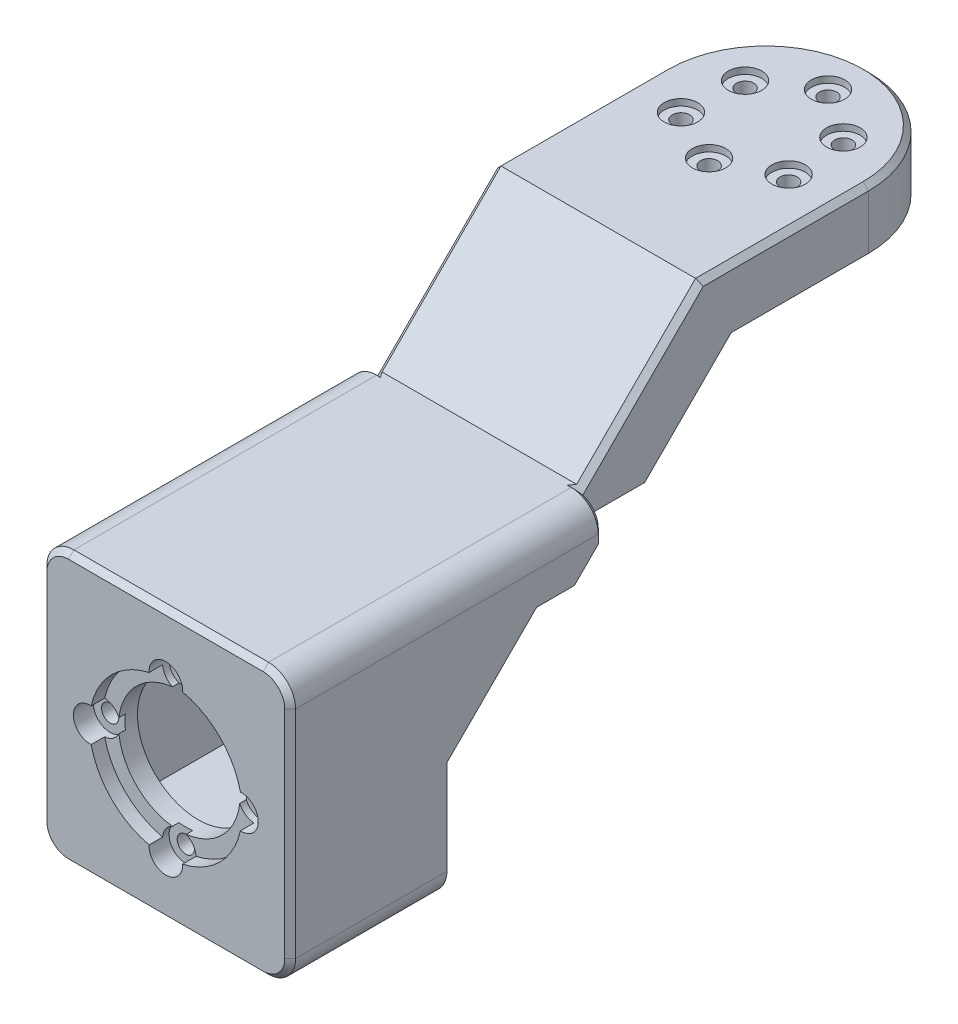
SolidWorks part; units mm, degrees
ref_plane "前视基准面" through (0, 0, 0) normal (0, 0, 1) x (1, 0, 0)
ref_plane "上视基准面" through (0, 0, 0) normal (0, 1, 0) x (1, 0, 0)
ref_plane "右视基准面" through (0, 0, 0) normal (1, 0, 0) x (0, 0, -1)
other "Configuration Table"
sketch "草图1" plane through (0, 0, 0) normal (0, 1, 0) x (1, 0, 0)
  circle A0 centre (0, 0) radius 19
  dimension "D1" = 38
extrude "凸台-拉伸1" add sketch "草图1" along normal blind 6
sketch "草图2" plane through (0, 6, 0) normal (0, 1, 0) x (1, 0, 0)
  line L0 (-19, 0) -> (19, 0) construction
  line L2 (-19, 0) -> (19, 0)
  line L3 (-19, 0) -> (-19, -25)
  line L4 (-19, -25) -> (19, -25)
  line L5 (19, 0) -> (19, -25)
  circle A0 centre (0, 0) radius 19 construction
  dimension "D1" = 25
extrude "凸台-拉伸2" add sketch "草图2" against normal up to surface (6 mm away) up to face at (0, 0, 19)
sketch "草图3" plane through (0, 6, 0) normal (0, 1, 0) x (1, 0, 0)
  line L1 (-19, -25) -> (19, -25)
  line L2 (-19, -25) -> (-19, -31)
  line L3 (-19, -31) -> (19, -31)
  line L4 (19, -25) -> (19, -31)
  dimension "D1" = 6
extrude "凸台-拉伸3" add sketch "草图3" against normal blind 28
sketch "草图4" plane through (0, 0, 31) normal (0, 0, 1) x (1, 0, 0)
  line L0 (19, -22) -> (19, 6) construction
  line L1 (-19, -22) -> (19, -22)
  line L2 (-19, -22) -> (-19, -16)
  line L3 (-19, -16) -> (19, -16)
  line L4 (19, -22) -> (19, -16)
  dimension "D1" = 6
extrude "凸台-拉伸4" add sketch "草图4" along normal blind 80
sketch "草图5" plane through (0, -22, 0) normal (0, -1, 0) x (1, 0, 0)
  line L0 (19, 111) -> (19, 25) construction
  line L1 (-19, 111) -> (19, 111)
  line L2 (-19, 111) -> (-19, 105)
  line L3 (-19, 105) -> (19, 105)
  line L4 (19, 111) -> (19, 105)
  dimension "D1" = 6
extrude "凸台-拉伸5" add sketch "草图5" along normal blind 40
sketch "草图6" plane through (0, 0, 0) normal (0, -1, 0) x (1, 0, 0)
  line L0 (-14.15, 0) -> (-14.15, 25)
  line L1 (19, 25) -> (-19, 25) construction
  line L2 (14.15, 0) -> (14.15, 25)
  line L3 (14.15, 25) -> (-14.15, 25)
  circle A0 centre (0, 0) radius 14.15
  arc M2 (-19, 0) -> (19, 0) centre (0, 0) ccw
  line M3 (19, 0) -> (19, 25)
  line M4 (19, 25) -> (-19, 25)
  line M5 (-19, 25) -> (-19, 0)
  dimension "D1" = 28.3
extrude "凸台-拉伸6" add sketch "草图6" along normal blind 6 contours A0 L0 L2 M4 M5 M2 M3 region at (0, 0, -14.7314)
sketch "草图7" plane through (-19, 0, 0) normal (-1, 0, 0) x (0, 0, 1)
  line L0 (31, 6) -> (53, -16)
  line L1 (111, -16) -> (31, -16) construction
  line L2 (53, -16) -> (31, -16)
  line L3 (31, -16) -> (31, 6)
sketch "草图8" plane through (19, 0, 0) normal (1, 0, 0) x (0, 0, -1)
  line L3 (-31, 6) -> (-53, -16)
  line L4 (-53, -16) -> (-31, -16)
  line L5 (-31, -16) -> (-31, 6)
  line L6 (-31, 6) -> (-53, -16)
  line L7 (-53, -16) -> (-31, -16)
  line L8 (-31, -16) -> (-31, 6)
  dimension "D1" = 0
extrude "凸台-拉伸8" add sketch "草图8" against normal up to surface (38 mm away) up to face at (-19, -20, 54.4)
sketch "草图11" plane through (0, 0, 105) normal (0, 0, -1) x (-1, 0, 0)
  line L0 (0, -22) -> (0, -41.5) construction
  line L1 (19, -22) -> (-19, -22) construction
  circle A0 centre (0, -41.5) radius 11.25
  dimension "D2" = 22.5
  dimension "D1" = 19.5
extrude "切除-拉伸2" cut sketch "草图11" against normal through all
sketch "草图12" plane through (0, 0, 111) normal (0, 0, 1) x (1, 0, 0)
  line L0 (0, -41.5) -> (14, -41.5) construction
  circle A0 centre (14, -41.5) radius 1.6
  circle A1 centre (0, -55.5) radius 1.6
  circle A2 centre (-14, -41.5) radius 1.6
  circle A3 centre (0, -27.5) radius 1.6
  point P13 (0, -41.5)
  dimension "D2" = 3.2
  dimension "D1" = 14
  dimension "D3" = 4
extrude "切除-拉伸3" cut sketch "草图12" against normal through all
sketch "草图13" plane through (0, 0, 111) normal (0, 0, 1) x (1, 0, 0)
  line L0 (0, -41.5) -> (11.25, -41.5) construction
  circle A0 centre (0, -27.5) radius 3.1
  circle A1 centre (0, -41.5) radius 11.25 construction
  circle A2 centre (14, -41.5) radius 3.1
  circle A3 centre (0, -55.5) radius 3.1
  circle A4 centre (-14, -41.5) radius 3.1
  point P17 (0, -41.5)
  dimension "D1" = 6.2
  dimension "D2" = 4
extrude "切除-拉伸4" cut sketch "草图13" against normal blind 3.7
sketch "草图14" plane through (0, 0, 111) normal (0, 0, 1) x (1, 0, 0)
  circle A0 centre (0, -41.5) radius 14.15
  dimension "D1" = 28.3
extrude "切除-拉伸5" cut sketch "草图14" against normal blind 2.5
sketch "草图15" plane through (19, 0, 0) normal (1, 0, 0) x (0, 0, -1)
  line L0 (-105, -22) -> (-105, -62) construction
  line L2 (-105, -62) -> (-99, -62)
  line L3 (-99, -62) -> (-65, -28)
  line L4 (-65, -28) -> (-65, -22)
  line L5 (-105, -22) -> (-25, -22) construction
  line L6 (-65, -22) -> (-105, -22) construction
  line L7 (-105, -62) -> (-111, -62)
  line L8 (-111, -62) -> (-111, -16)
  line L9 (-111, -16) -> (-53, -16) construction
  line L10 (-111, -16) -> (-65, -16)
  line L11 (-65, -16) -> (-65, -22)
  dimension "D1" = 6
extrude "凸台-拉伸12" add sketch "草图15" along normal blind 4
sketch "草图16" plane through (-19, 0, 0) normal (-1, 0, 0) x (0, 0, 1)
  line L7 (99, -62) -> (105, -62)
  line L8 (65, -28) -> (99, -62)
  line L9 (65, -22) -> (65, -28)
  line L10 (65, -16) -> (65, -22)
  line L11 (111, -16) -> (65, -16)
  line L12 (111, -62) -> (111, -16)
  line L13 (105, -62) -> (111, -62)
  line L14 (99, -62) -> (105, -62)
  line L15 (65, -28) -> (99, -62)
  line L16 (65, -22) -> (65, -28)
  line L17 (65, -16) -> (65, -22)
  line L18 (111, -16) -> (65, -16)
  line L19 (111, -62) -> (111, -16)
  line L20 (105, -62) -> (111, -62)
  dimension "D1" = 0
extrude "凸台-拉伸13" add sketch "草图16" along normal blind 4
sketch "草图18" plane through (-19, 0, 0) normal (-1, 0, 0) x (0, 0, 1)
  line L1 (25, -6) -> (41, -22)
  line L2 (25, -22) -> (65, -22) construction
  line L3 (31, 6) -> (53, -16) construction
  line L4 (41, -22) -> (41.8531, -34.2873)
  line L5 (41.8531, -34.2873) -> (18.4073, -35.915)
  line L6 (18.4073, -35.915) -> (21.1184, -13.0175)
  line L7 (21.1184, -13.0175) -> (25, -6)
extrude "切除-拉伸7" cut sketch "草图18" against normal through all
sketch "草图19" plane through (0, -62, 0) normal (0, -1, 0) x (1, 0, 0)
  line L0 (23, 99) -> (23, 65) construction
  line L1 (-23, 111) -> (23, 111)
  line L2 (-23, 111) -> (-23, 81)
  line L3 (-23, 81) -> (23, 81)
  line L4 (23, 111) -> (23, 81)
  dimension "D1" = 30
extrude "凸台-拉伸14" add sketch "草图19" along normal blind 4
sketch "草图20" plane through (-23, 0, 0) normal (-1, 0, 0) x (0, 0, 1)
  line L1 (81, -66) -> (102.3181, -66)
  line L2 (81, -66) -> (81, -36.6886)
  line L3 (81, -36.6886) -> (102.3181, -36.6886)
  line L4 (102.3181, -66) -> (102.3181, -36.6886)
extrude "凸台-拉伸15" add sketch "草图20" against normal up to surface (4 mm away) up to face at (-19, -39.2, 87.8)
sketch "草图21" plane through (23, 0, 0) normal (1, 0, 0) x (0, 0, -1)
  line L1 (-81, -66) -> (-101.783, -66)
  line L2 (-81, -66) -> (-81, -39.6316)
  line L3 (-81, -39.6316) -> (-101.783, -39.6316)
  line L4 (-101.783, -66) -> (-101.783, -39.6316)
extrude "凸台-拉伸16" add sketch "草图21" against normal up to surface (4 mm away) up to face at (19, -39.2, 87.8)
sketch "草图22" plane through (-19, 0, 0) normal (-1, 0, 0) x (0, 0, 1)
  line L1 (65, -28) -> (53, -28)
  line L2 (65, -28) -> (65, -16)
  line L3 (65, -16) -> (53, -16)
  line L4 (53, -28) -> (53, -16)
extrude "凸台-拉伸17" add sketch "草图22" along normal up to surface (4 mm away) up to face at (-23, -39.3333, 85.6667)
chamfer "倒角1" distance 5 angle 45 1 edges at (-21, -28, 53)
sketch "草图23" plane through (19, 0, 0) normal (1, 0, 0) x (0, 0, -1)
  line L0 (-65, -16) -> (-53, -16) construction
  line L1 (-65, -28) -> (-53, -28)
  line L2 (-65, -28) -> (-65, -16)
  line L3 (-65, -16) -> (-53, -16)
  line L4 (-53, -28) -> (-53, -16)
extrude "凸台-拉伸18" add sketch "草图23" along normal up to surface (4 mm away) up to face at (23, -39.3333, 85.6667)
chamfer "倒角2" distance 5 angle 45 1 edges at (21, -28, 53)
sketch "草图24" plane through (0, 0, 0) normal (0, -1, 0) x (1, 0, 0)
  line L0 (0, 0) -> (0, 10.5) construction
  line L1 (0, 0) -> (9.9593, 5.75) construction
  circle A0 centre (0, 10.5) radius 1.6
  circle A1 centre (9.0933, -5.25) radius 1.6
  circle A2 centre (-9.0933, -5.25) radius 1.6
  circle A3 centre (9.9593, 5.75) radius 1.6
  circle A4 centre (0, -11.5) radius 1.6
  circle A5 centre (-9.9593, 5.75) radius 1.6
  point P10 (0, 0)
  point P18 (0, 0)
  dimension "D1" = 3.2
  dimension "D6" = 3.2
  dimension "D2" = 10.5
  dimension "D4" = 60
  dimension "D5" = 11.5
  dimension "D3" = 3
  dimension "D7" = 3
extrude "切除-拉伸8" cut sketch "草图24" against normal through all
sketch "草图25" plane through (0, 6, 0) normal (0, 1, 0) x (1, 0, 0)
  circle A0 centre (0, 11.5) radius 3.1
  circle A1 centre (-9.0933, 5.25) radius 3.1
  circle A2 centre (-9.9593, -5.75) radius 3.1
  circle A3 centre (0, -10.5) radius 3.1
  circle A4 centre (9.9593, -5.75) radius 3.1
  circle A5 centre (9.0933, 5.25) radius 3.1
  dimension "D1" = 6.2
extrude "切除-拉伸9" cut sketch "草图25" against normal blind 1.2
fillet "圆角1" radius 5 4 edges at (23, -16, 82) (-23, -16, 82) (-23, -66, 96) (23, -66, 96)
chamfer "倒角3" distance 1 angle 45 31 edges at (-23, -25.5, 55.5) (-23, -28, 61.5) (-23, -36, 73) (-19, -22, 47) (-19, -14, 33) (-19, -5.0505, 42.0505) (-19, 6, 15.5) (0, 6, -19) (19, 6, 15.5) (19, -5.0505, 42.0505) (-19, -6, 12.5) (0, -6, -19) (19, -6, 12.5) (19, -14, 33) (19, -22, 47) (23, -25.5, 55.5) (23, -28, 61.5) (23, -36, 73) (-23, -52.5, 81) (23, -52.5, 81) (-21.5355, -64.5355, 81) (21.5355, -64.5355, 81) (0, -66, 81) (0, -16, 111) (21.5355, -17.4645, 111) (-21.5355, -17.4645, 111) (23, -41, 111) (-23, -41, 111) (21.5355, -64.5355, 111) (-21.5355, -64.5355, 111) (0, -66, 111)
chamfer "倒角4" distance 1 angle 45 4 edges at (23, -21.2929, 53) (21.5355, -17.4645, 53) (-23, -21.2929, 53) (-21.5355, -17.4645, 53)
sketch "草图26" plane through (0, 0, 0) normal (0, -1, 0) x (1, 0, 0)
  line L0 (14.15, 0) -> (14.15, 25) construction
  line L1 (-14.15, 25) -> (14.15, 25)
  line L2 (-14.15, 25) -> (-14.15, 24)
  line L3 (-14.15, 24) -> (14.15, 24)
  line L4 (14.15, 25) -> (14.15, 24)
  dimension "D1" = 1
extrude "凸台-拉伸19" add sketch "草图26" along normal up to surface (6 mm away) up to face at (0, -6, 8.4813)
sketch "草图27" plane through (0, 0, 24) normal (0, 0, -1) x (-1, 0, 0)
  circle A0 centre (-9, -2.5) radius 1.175 construction
  circle A1 centre (0.5, -2.5) radius 1.175 construction
  circle A2 centre (-9, -2.5) radius 1.175 construction
  circle A3 centre (0.5, -2.5) radius 1.175 construction
  circle A4 centre (-9, -2.5) radius 1.35
  circle A5 centre (0.5, -2.5) radius 1.35
  dimension "D1" = 2.7
extrude "切除-拉伸10" cut sketch "草图27" against normal blind 2.5
